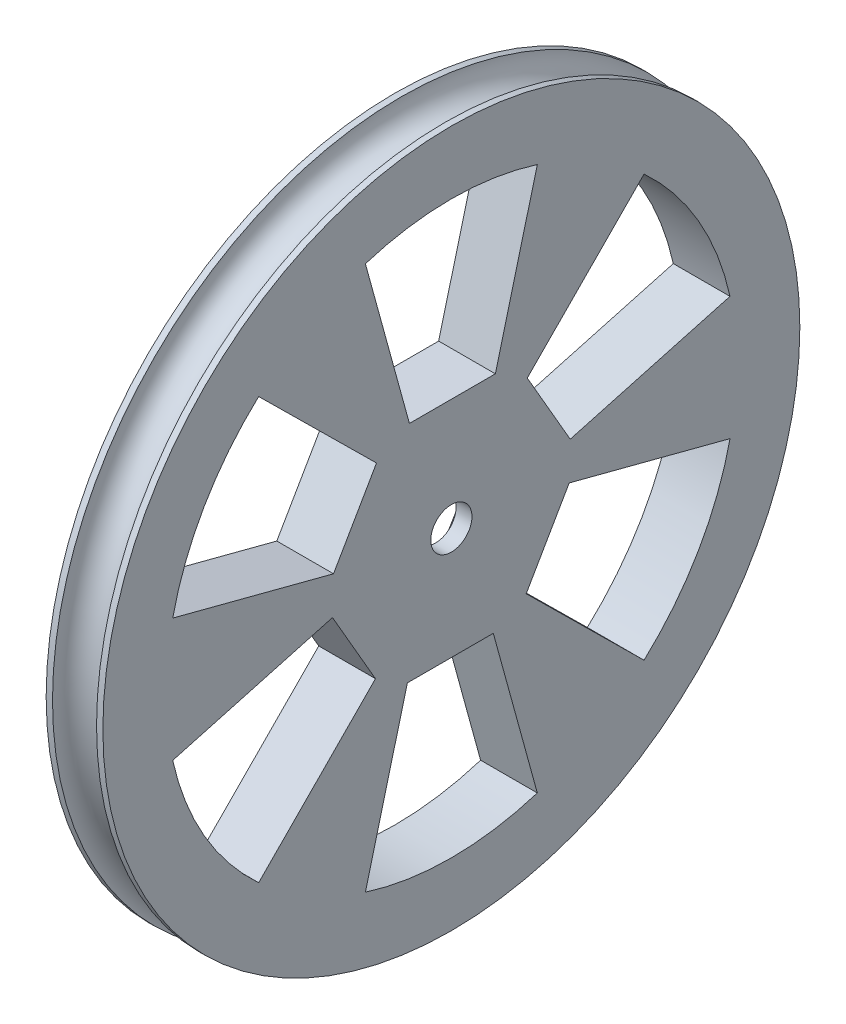
SolidWorks part; units mm, degrees
ref_plane "Front Plane" through (0, 0, 0) normal (0, 0, 1) x (1, 0, 0)
ref_plane "Top Plane" through (0, 0, 0) normal (0, 1, 0) x (1, 0, 0)
ref_plane "Right Plane" through (0, 0, 0) normal (1, 0, 0) x (0, 0, -1)
sketch "Sketch2" plane through (0, 0, 0) normal (0, 0, 1) x (1, 0, 0)
  line L1 (0, 0) -> (3.5306, 0)
  line L2 (0, 0) -> (0, 27.94)
  line L3 (3.5306, 27.94) -> (4.0386, 27.94)
  line L4 (3.5306, 0) -> (3.5306, 27.94)
  line L5 (3.5306, 27.94) -> (3.5306, 0)
  line L6 (3.5306, 0) -> (4.0386, 0)
  line L7 (4.0386, 27.94) -> (4.0386, 0)
  line L8 (0, 27.94) -> (-0.508, 27.94)
  line L9 (0, 27.94) -> (0, 0)
  line L10 (0, 0) -> (-0.508, 0)
  line L11 (-0.508, 27.94) -> (-0.508, 0)
  arc A0 (0, 27.94) -> (3.5306, 27.94) centre (1.7653, 27.94) ccw
  dimension "D1" = 3.5306
  dimension "D2" = 27.94
  dimension "D3" = 0.508
revolve "Revolve1" add sketch "Sketch2" angle 360 about L1 region at (1.7653, 13.2797, 0) region at (-0.254, 13.97, 0) region at (3.7846, 13.97, 0)
sketch "Sketch3" plane through (-0.508, 0, 0) normal (1, 0, 0) x (0, 0, -1)
  line L0 (3.5288, 8.9669) -> (6.8917, 21.8165)
  line L1 (3.5762, 6.0001) -> (-3.4081, 6.0971)
  line L2 (-3.4081, 6.0971) -> (-6.9843, 0.097)
  line L3 (-6.9843, 0.097) -> (-3.5762, -6.0001)
  line L4 (-3.5762, -6.0001) -> (3.4081, -6.0971)
  line L5 (3.4081, -6.0971) -> (6.9843, -0.097)
  line L6 (6.9843, -0.097) -> (3.5762, 6.0001)
  line L7 (3.5288, 8.9669) -> (-3.3629, 8.9669)
  line L9 (-3.3629, 8.9669) -> (-6.8917, 21.8165)
  circle A0 centre (0, 0) radius 6.0492 construction
  arc A1 (6.8917, 21.8165) -> (-6.8917, 21.8165) centre (0, 0) ccw
  circle A2 centre (0, 0) radius 1.651
extrude "Cut-Extrude1" cut sketch "Sketch3" along normal up to next contours A1 L0 L7 L9 | A2 region at (-0.508, 16.5276, -0.0343) region at (-0.508, 0, 0)
ref_axis "Axis1" through (0, 0, 0) along (1, 0, 0)
pattern_circular "CirPattern1" count 6 over 360 about axis through (0, 0, 0) along (1, 0, 0) of face at (1.7653, 15.3917, 5.1273) of face at (1.7653, 22.3478, 0) of face at (1.7653, 15.3917, -5.2103) of face at (1.7653, 8.9669, -0.0829)
extrude "Cut-Extrude2" cut sketch "Sketch3<3>" along normal offset from surface (3.2766 mm away) 1.27 contours L6 L5 L4 L3 L2 L1 A2 region at (-0.508, 2.861, -5.1184) up to face at (4.0386, 7.7928, -13.5804)
sketch "Sketch3<3>" plane through (-0.508, 0, 0) normal (1, 0, 0) x (0, 0, -1) same geometry as "Sketch3"
